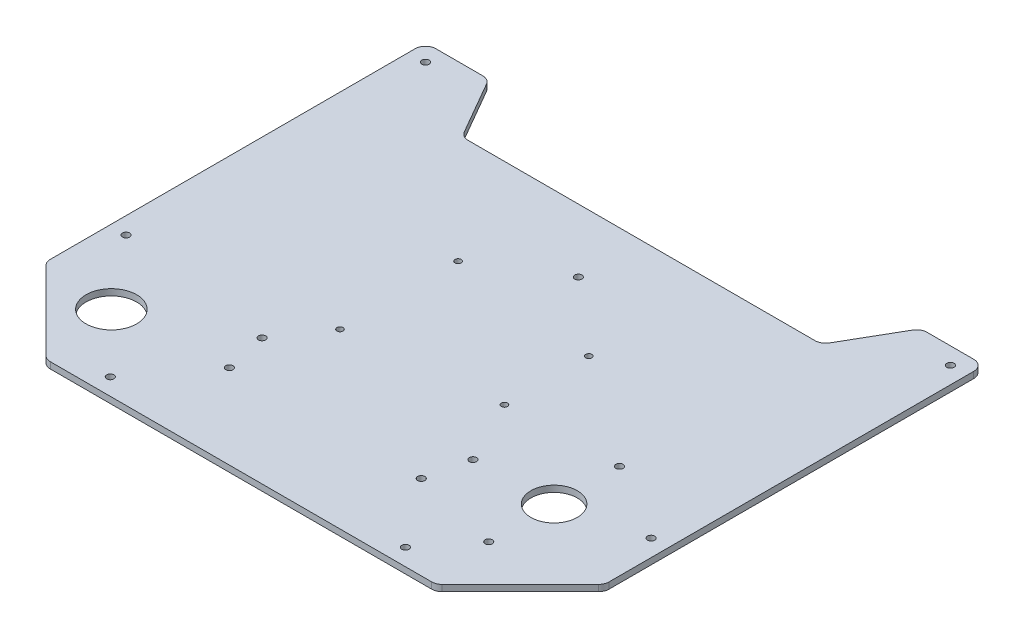
SolidWorks part; units mm, degrees
material "Acier non allié"
ref_plane "Front" through (0, 0, 0) normal (0, 0, 1) x (1, 0, 0)
ref_plane "Top" through (0, 0, 0) normal (0, 1, 0) x (1, 0, 0)
ref_plane "Right" through (0, 0, 0) normal (1, 0, 0) x (0, 0, -1)
sketch "Esquisse1" plane through (0, 0, 0) normal (0, 1, 0) x (1, 0, 0)
  line L0 (0, 0) -> (0, 1919.0564) construction
  line L1 (-92.5, 0) -> (92.5, 0)
  line L2 (92.5, 0) -> (132.5, 40)
  line L3 (132.5, 40) -> (132.5, 220)
  line L4 (132.5, 220) -> (102.5, 220)
  line L5 (102.5, 220) -> (85.1795, 190)
  line L6 (85.1795, 190) -> (-85.1795, 190)
  line L7 (-102.5, 220) -> (-85.1795, 190)
  line L8 (-132.5, 220) -> (-102.5, 220)
  line L9 (-132.5, 40) -> (-132.5, 220)
  line L10 (-92.5, 0) -> (-132.5, 40)
  point P12 (0, 190)
  dimension "D1" = 132.5
  dimension "D2" = 220
  dimension "D3" = 30
  dimension "D4" = 30
  dimension "D5" = 40
  dimension "D6" = 40
  dimension "D7" = 60
extrude "Boss.-Extru.1" add sketch "Esquisse1" along normal blind 3
fillet "Congé1" radius 5 10 edges at (132.5, 1.5, -220) (102.5, 1.5, -220) (85.1795, 1.5, -190) (-85.1795, 1.5, -190) (-102.5, 1.5, -220) (-132.5, 1.5, -220) (-132.5, 1.5, -40) (-92.5, 1.5, 0) (92.5, 1.5, 0) (132.5, 1.5, -40)
sketch "Esquisse2" plane through (0, 0, 0) normal (0, -1, 0) x (1, 0, 0)
  line L0 (0, 0) -> (0, -330.9968) construction
  line L1 (-90.4289, 0) -> (90.4289, 0) construction
  line L2 (-105.3868, -220) -> (-127.5, -220) construction
  line L3 (-132.5, -215) -> (-132.5, -42.0711) construction
  circle A0 centre (-70, -8) radius 1
  circle A1 centre (-124.5, -70) radius 1
  circle A2 centre (-124.5, -212) radius 1
  circle A3 centre (124.5, -212) radius 1
  circle A4 centre (124.5, -70) radius 1
  circle A5 centre (70, -8) radius 1
  dimension "D3" = 2
  dimension "D6" = 2
  dimension "D9" = 2
  dimension "D1" = 70
  dimension "D2" = 8
  dimension "D4" = 124.5
  dimension "D5" = 70
  dimension "D7" = 8
  dimension "D8" = 8
extrude "Enlèv. mat.-Extru.1" cut sketch "Esquisse2" against normal through all
hole_wizard "Dégagement M31" positions "Esquisse3" profile "Esquisse4" hole size "M3" standard "ISO" end condition through all
sketch "Esquisse3" plane through (0, 0, 0) normal (0, -1, 0) x (-1, 0, 0)
  point P0 (-70, 8)
  point P3 (-124.5, 70)
  point P6 (-124.5, 212)
  point P9 (124.5, 212)
  point P12 (124.5, 70)
  point P15 (70, 8)
sketch "Esquisse4" plane through (70, 0, -8) normal (1, 0, 0) x (0, 0, -1)
  line L0 (0, 0) -> (0, 3)
  line L1 (0, 3) -> (1.7, 3)
  line L2 (1.7, 3) -> (1.7, 0)
  line L5 (1.7, 0) -> (0, 0)
  line L11 (0, -6.35) -> (0, 107.95) construction
  dimension "Diamètre du perçage jusqu'au prochain" = 3.4
  dimension "Profondeur du perçage jusqu'au prochain" = 3
sketch "Esquisse5" plane through (0, 0, 0) normal (0, -1, 0) x (1, 0, 0)
  line L0 (-35.055, -138) -> (-35.055, -82) construction
  line L5 (34.945, -130) -> (34.945, -90) construction
  line L6 (132.5, -42.0711) -> (132.5, -215) construction
  line L7 (87.5, -92) -> (87.5, -30) construction
  line L20 (-132.5, -215) -> (-132.5, -42.0711) construction
  line L21 (-90.4289, 0) -> (90.4289, 0) construction
  line L22 (-105.3868, -220) -> (-127.5, -220) construction
  line L27 (-45.5, -40) -> (45.5, -40) construction
  line L28 (127.5, -220) -> (105.3868, -220) construction
  line L29 (-50, -60) -> (50, -60) construction
  line L30 (-50, -60) -> (-50, -160) construction
  line L31 (-50, -160) -> (50, -160) construction
  line L32 (50, -60) -> (50, -160) construction
  circle A0 centre (-97.5, -36) radius 12
  circle A1 centre (-45.5, -40) radius 1.5
  circle A2 centre (45.5, -40) radius 1.5
  circle A3 centre (87.5, -61) radius 11
  circle A4 centre (87.5, -92) radius 1.5
  circle A5 centre (87.5, -30) radius 1.5
  circle A6 centre (-35.055, -138) radius 1
  circle A7 centre (-35.055, -82) radius 1
  circle A8 centre (34.945, -130) radius 1
  circle A9 centre (34.945, -90) radius 1
  circle A10 centre (0, -160) radius 1.5
  circle A11 centre (-50, -60) radius 1.5
  circle A12 centre (50, -60) radius 1.5
  point P8 (87.5, -61)
  point P18 (-35.055, -110)
  point P23 (0, -160)
  point P29 (50, -110)
  dimension "D10" = 24
  dimension "D15" = 3
  dimension "D16" = 3
  dimension "D2" = 22
  dimension "D6" = 3
  dimension "D7" = 3
  dimension "D20" = 2
  dimension "D21" = 2
  dimension "D27" = 2
  dimension "D28" = 2
  dimension "D14" = 3
  dimension "D30" = 3
  dimension "D31" = 3
  dimension "D8" = 35
  dimension "D9" = 36
  dimension "D17" = 91
  dimension "D18" = 40
  dimension "D19" = 87
  dimension "D3" = 45
  dimension "D4" = 61
  dimension "D5" = 62
  dimension "D22" = 110
  dimension "D23" = 97.445
  dimension "D24" = 56
  dimension "D25" = 8
  dimension "D26" = 40
  dimension "D29" = 70
  dimension "D11" = 100
  dimension "D12" = 100
  dimension "D13" = 110
extrude "Enlèv. mat.-Extru.2" cut sketch "Esquisse5" against normal through all
fillet "Congé2" [suppressed] radius 3
hole_wizard "Dégagement M32" positions "Esquisse6" profile "Esquisse7" hole size "M3" standard "ISO" end condition up to next
sketch "Esquisse6" plane through (0, 3, 0) normal (0, 1, 0) x (1, 0, 0)
  point P0 (-45.5, 40)
  point P3 (45.5, 40)
  point P7 (87.5, 92)
  point P10 (87.5, 30)
  point P13 (-50, 60)
  point P16 (50, 60)
  point P19 (0, 160)
sketch "Esquisse7" plane through (-45.5, 3, -40) normal (1, 0, 0) x (0, 0, 1)
  line L0 (0, 0) -> (0, 3)
  line L1 (0, 3) -> (1.7, 3)
  line L2 (1.7, 3) -> (1.7, 0)
  line L5 (1.7, 0) -> (0, 0)
  line L11 (0, -6.35) -> (0, 107.95) construction
  dimension "Diamètre du perçage jusqu'au prochain" = 3.4
  dimension "Profondeur du perçage jusqu'au prochain" = 3
hole_wizard "Dégagement M2.51" positions "Esquisse8" profile "Esquisse9" hole size "M2.5" standard "ISO" end condition up to next
sketch "Esquisse8" plane through (0, 3, 0) normal (0, 1, 0) x (1, 0, 0)
  point P0 (-35.055, 138)
  point P3 (-35.055, 82)
  point P6 (34.945, 90)
  point P9 (34.945, 130)
sketch "Esquisse9" plane through (-35.055, 3, -138) normal (1, 0, 0) x (0, 0, 1)
  line L0 (0, 0) -> (0, 3)
  line L1 (0, 3) -> (1.45, 3)
  line L2 (1.45, 3) -> (1.45, 0)
  line L5 (1.45, 0) -> (0, 0)
  line L11 (0, -6.35) -> (0, 107.95) construction
  dimension "Diamètre du perçage jusqu'au prochain" = 2.9
  dimension "Profondeur du perçage jusqu'au prochain" = 3
equation "\"WIDTH\"= 300mm'Total width of the robot"
equation "\"LENGTH\"= 220mm'Total length of the robot"
equation "\"CUT_DEPTH\"= 45mm'Depth of the cut on the edges of the plate"
equation "\"Plate_th\"= 3mm'Thickness of the plate"
equation "\"D1\"= \"Plate_th\""
equation "\"D23@Esquisse5\"=(265-70.11)/2"
